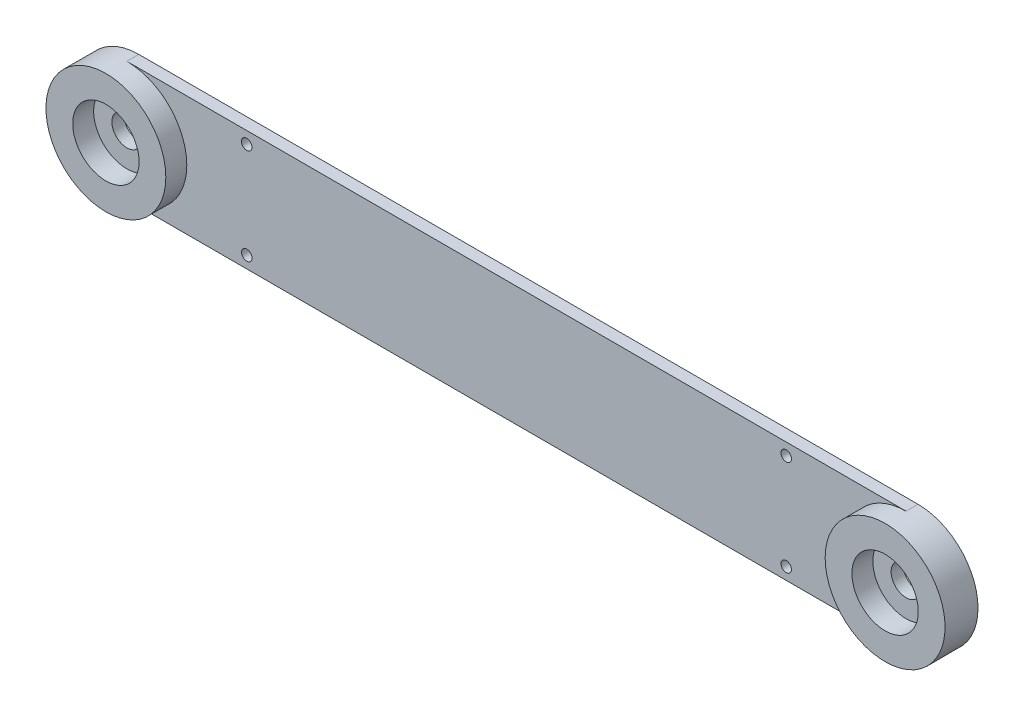
SolidWorks part; units mm, degrees
ref_plane "Ebene vorne" through (0, 0, 0) normal (0, 0, 1) x (1, 0, 0)
ref_plane "Ebene oben" through (0, 0, 0) normal (0, 1, 0) x (1, 0, 0)
ref_plane "Ebene rechts" through (0, 0, 0) normal (1, 0, 0) x (0, 0, -1)
sketch "Skizze1" plane through (0, 0, 0) normal (0, 0, 1) x (1, 0, 0)
  line L0 (-130, 0) -> (0, 0) construction
  line L1 (-130, -20) -> (130, -20)
  line L2 (-130, -20) -> (-130, 20) construction
  line L3 (-130, 20) -> (130, 20)
  line L4 (130, -20) -> (130, 20) construction
  line L5 (-130, -20) -> (130, 20) construction
  line L6 (-130, 20) -> (130, -20) construction
  line L7 (0, 0) -> (130, 0) construction
  arc A0 (-130, 20) -> (-130, -20) centre (-130, 0) ccw
  arc A1 (130, 20) -> (130, -20) centre (130, 0) cw
  point P0 (0, 0)
  dimension "D1" = 260
  dimension "D2" = 40
extrude "Aufsatz-Linear austragen1" add sketch "Skizze1" along normal blind 4
sketch "Skizze2" plane through (0, 0, 4) normal (0, 0, 1) x (1, 0, 0)
  circle A0 centre (-130, 0) radius 20
  circle A1 centre (-130, 0) radius 11.075
  dimension "D1" = 22.15
extrude "Aufsatz-Linear austragen2" add sketch "Skizze2" along normal blind 7
sketch "Skizze3" plane through (0, 0, 4) normal (0, 0, 1) x (1, 0, 0)
  circle A0 centre (-130, 0) radius 5
  dimension "D1" = 10
extrude "Schnitt-Linear austragen1" cut sketch "Skizze3" against normal through all and the other way through all
mirror "Spiegeln1" about plane through (0, 0, 0) normal (1, 0, 0) of "Aufsatz-Linear austragen2", "Schnitt-Linear austragen1"
sketch "Skizze4" plane through (0, 0, 4) normal (0, 0, 1) x (1, 0, 0)
  line L0 (-130, 20) -> (130, 20) construction
  line L1 (0, 0) -> (-130, 0) construction
  line L2 (0, 0) -> (0, 20) construction
  circle A0 centre (-130, 0) radius 30 construction
  circle A1 centre (-90, 16) radius 4 construction
  circle A2 centre (-90, 16) radius 1.75
  circle A3 centre (-90, -16) radius 4 construction
  circle A4 centre (-90, -16) radius 1.75
  circle A5 centre (90, -16) radius 4 construction
  circle A6 centre (90, 16) radius 4 construction
  circle A7 centre (90, -16) radius 1.75
  circle A8 centre (90, 16) radius 1.75
  dimension "D1" = 60
  dimension "D2" = 8
  dimension "D3" = 3.5
  dimension "D4" = 40
extrude "Schnitt-Linear austragen2" cut sketch "Skizze4" against normal through all
